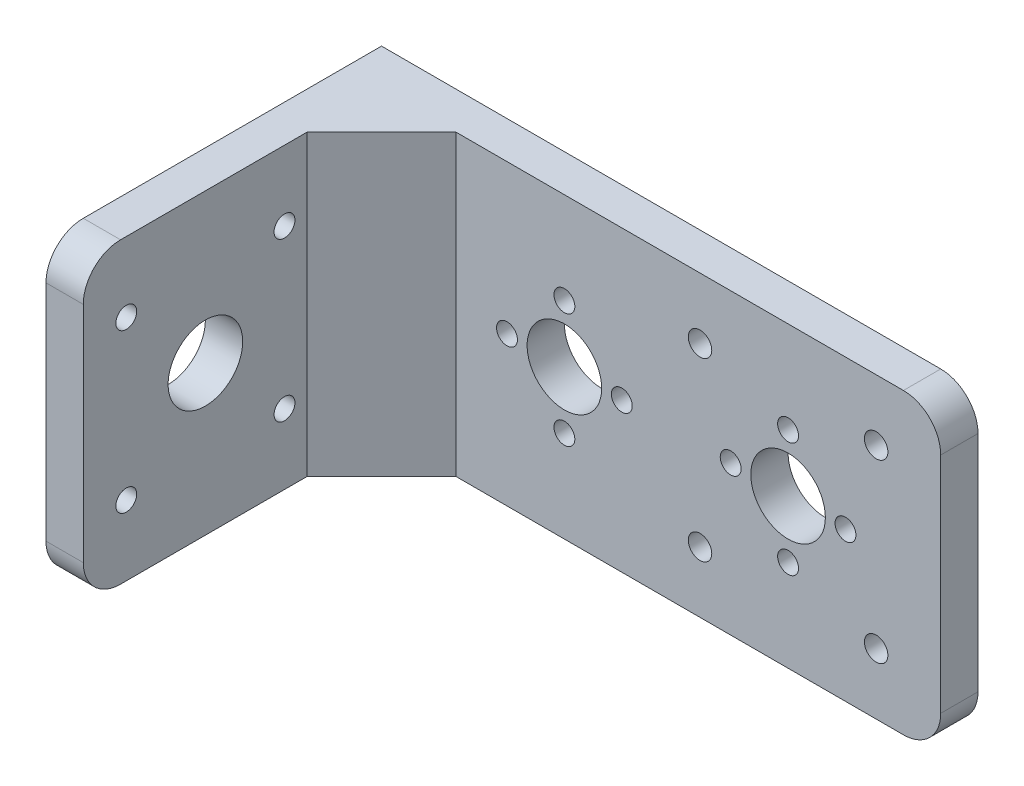
SolidWorks part; units mm, degrees
material "Copper"
ref_plane "Front Plane" through (0, 0, 0) normal (0, 0, 1) x (1, 0, 0)
ref_plane "Top Plane" through (0, 0, 0) normal (0, 1, 0) x (1, 0, 0)
ref_plane "Right Plane" through (0, 0, 0) normal (1, 0, 0) x (0, 0, -1)
sketch "Sketch1" plane through (0, 0, 0) normal (0, 0, 1) x (1, 0, 0)
  line L1 (0, 0) -> (-101.6, 0)
  line L2 (0, 0) -> (0, -50.8)
  line L3 (0, -50.8) -> (-101.6, -50.8)
  line L4 (-101.6, 0) -> (-101.6, -50.8)
  dimension "D1" = 50.8
  dimension "D2" = 101.6
extrude "Boss-Extrude1" add sketch "Sketch1" along normal blind 6.35
sketch "Sketch2" plane through (0, 0, 6.35) normal (0, 0, 1) x (1, 0, 0)
  line L0 (0, -25.4) -> (-101.6, -25.4) construction
  line L3 (0, -50.8) -> (0, 0) construction
  line L4 (-101.6, 0) -> (-101.6, -50.8) construction
  circle A0 centre (-11, -10.4) radius 2
  circle A1 centre (-41, -10.4) radius 2
  circle A2 centre (-41, -40.4) radius 2
  circle A3 centre (-11, -40.4) radius 2
  dimension "D1" = 15
  dimension "D7" = 4
  dimension "D8" = 4
  dimension "D9" = 4
  dimension "D10" = 4
  dimension "D2" = 15
  dimension "D3" = 15
  dimension "D4" = 15
  dimension "D5" = 30
  dimension "D6" = 30
  dimension "D11" = 11
  dimension "D12" = 11
extrude "Cut-Extrude1" cut sketch "Sketch2" against normal blind 6.35
sketch "Sketch3" plane through (0, 0, 6.35) normal (0, 0, 1) x (1, 0, 0)
  line L0 (0, -25.4) -> (-101.6, -25.4) construction
  line L1 (0, -50.8) -> (0, 0) construction
  line L2 (-101.6, 0) -> (-101.6, -50.8) construction
  circle A0 centre (-26, -15.621) radius 1.778
  dimension "D1" = 26
  dimension "D3" = 3.556
  dimension "D2" = 9.779
extrude "Cut-Extrude2" cut sketch "Sketch3" against normal blind 6.35
sketch "Sketch4" plane through (0, 0, 6.35) normal (0, 0, 1) x (1, 0, 0)
  line L0 (0, -25.4) -> (-101.6, -25.4) construction
  line L3 (0, -50.8) -> (0, 0) construction
  line L4 (-101.6, 0) -> (-101.6, -50.8) construction
  circle A0 centre (-26, -25.4) radius 6.35
  dimension "D1" = 12.7
  dimension "D2" = 26
extrude "Cut-Extrude3" cut sketch "Sketch4" against normal blind 6.35
pattern_circular "CirPattern1" count 4 over 360 about axis through (-26, -25.4, 6.35) along (0, 0, 1) of "Cut-Extrude2"
sketch "Sketch5" plane through (0, 0, 6.35) normal (0, 0, 1) x (1, 0, 0)
  line L0 (-101.6, -50.8) -> (0, -50.8) construction
  line L1 (-101.6, 0) -> (-95.25, 0)
  line L2 (-101.6, 0) -> (-101.6, -50.8)
  line L3 (-101.6, -50.8) -> (-95.25, -50.8)
  line L4 (-95.25, 0) -> (-95.25, -50.8)
  dimension "D1" = 6.35
extrude "Boss-Extrude2" add sketch "Sketch5" along normal blind 50.8
sketch "Sketch6" plane through (-95.25, 0, 0) normal (1, 0, 0) x (0, 0, -1)
  line L0 (-6.35, -50.8) -> (-6.35, 0) construction
  line L1 (-57.15, -50.8) -> (-6.35, -50.8) construction
  circle A0 centre (-36.35, -25.4) radius 6.35
  dimension "D1" = 30
  dimension "D2" = 12.7
  dimension "D3" = 25.4
extrude "Cut-Extrude4" cut sketch "Sketch6" against normal blind 6.35
sketch "Sketch7" plane through (-95.25, 0, 0) normal (1, 0, 0) x (0, 0, -1)
  circle A0 centre (-49.8247, -11.9253) radius 1.778
  circle A1 centre (-36.35, -25.4) radius 6.35 construction
  dimension "D1" = 3.556
  dimension "D2" = 13.4747
  dimension "D3" = 13.4747
extrude "Cut-Extrude5" cut sketch "Sketch7" against normal blind 6.35
pattern_circular "CirPattern2" count 4 over 360 about axis through (-95.25, -25.4, 36.35) along (1, 0, 0) of "Cut-Extrude5"
pattern_linear "LPattern1" count 2 spacing 38.1 along (-1, 0, 0) of "CirPattern1", "Cut-Extrude3"
sketch "Sketch8" plane through (0, -50.8, 0) normal (0, -1, 0) x (1, 0, 0)
  line L0 (-95.25, 6.35) -> (-95.25, 19.05)
  line L1 (-95.25, 57.15) -> (-95.25, 6.35) construction
  line L2 (-95.25, 19.05) -> (-82.55, 6.35)
  line L3 (-95.25, 6.35) -> (0, 6.35) construction
  line L4 (-82.55, 6.35) -> (-95.25, 6.35)
  dimension "D1" = 12.7
  dimension "D2" = 12.7
extrude "Boss-Extrude3" add sketch "Sketch8" against normal blind 50.8
fillet "Fillet1" radius 6.35 4 edges at (0, -50.8, 3.175) (0, 0, 3.175) (-98.425, 0, 57.15) (-98.425, -50.8, 57.15)
